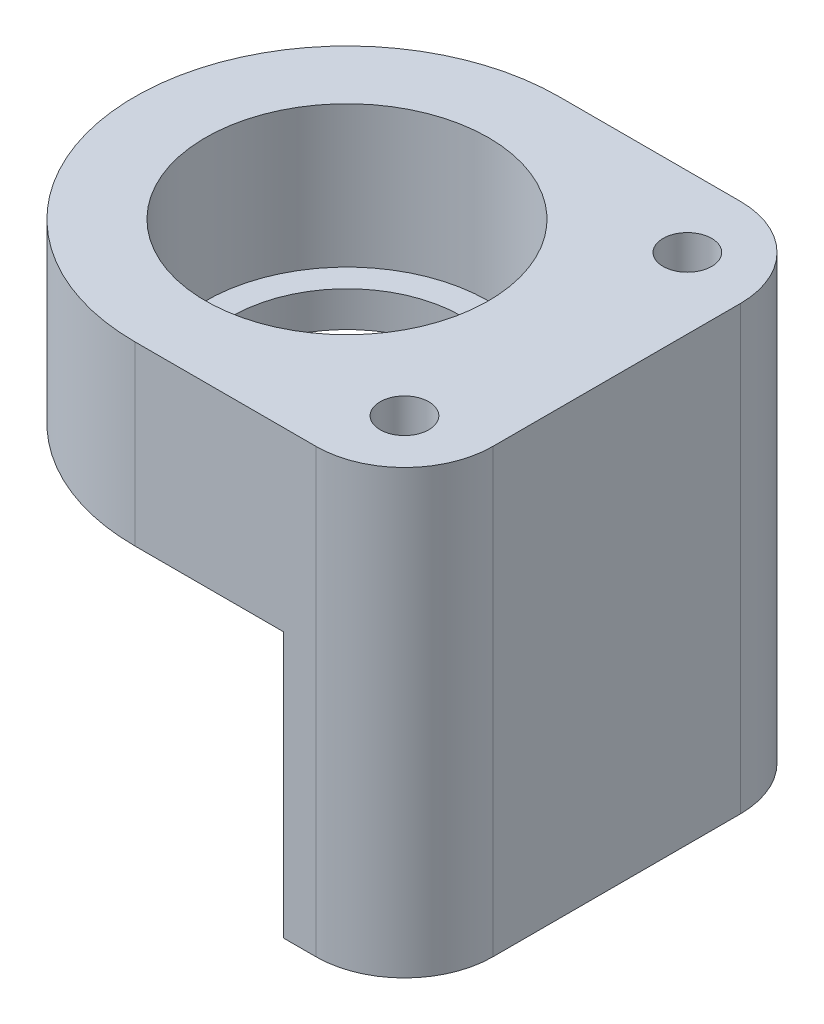
SolidWorks part; units mm, degrees
ref_plane "Front Plane" through (0, 0, 0) normal (0, 0, 1) x (1, 0, 0)
ref_plane "Top Plane" through (0, 0, 0) normal (0, 1, 0) x (1, 0, 0)
ref_plane "Right Plane" through (0, 0, 0) normal (1, 0, 0) x (0, 0, -1)
ref_axis "X" through (88.99, 0, 0) along (-1, 0, 0)
ref_axis "Y" through (0, 55, 0) along (0, -1, 0)
ref_axis "Z" through (0, 0, -88.99) along (0, 0, 1)
sketch "Sketch1" plane through (0, 0, 0) normal (0, 0, 1) x (1, 0, 0)
  line L0 (0, 0) -> (0, 52.8087) construction
  line L4 (-24, 0) -> (-24, 50)
  line L9 (-20, 30) -> (-16, 30)
  line L10 (-16, 34) -> (-16, 50)
  line L13 (-16, 50) -> (-24, 50)
  line L14 (-24, 0) -> (-20, 0)
  line L16 (-20, 0) -> (-20, 30)
  line L17 (-16, 30) -> (-13, 30)
  line L18 (-13, 30) -> (-13, 34)
  line L19 (-13, 34) -> (-16, 34)
  point P3 (0, 0)
  dimension "D2" = 32
  dimension "D3" = 30
  dimension "D4" = 48
  dimension "D5" = 40
  dimension "D6" = 4
  dimension "D7" = 26
  dimension "D10" = 50
revolve "Revolve1" add sketch "Sketch1" angle 360 about L0
sketch "Sketch6" plane through (0, 50, 0) normal (0, 1, 0) x (1, 0, 0)
  line L3 (0, -24) -> (20.5, -24)
  line L4 (30.5, -14) -> (30.5, 14)
  line L5 (20.5, 24) -> (0, 24)
  arc A3 (0, -24) -> (0, 24) centre (0, 0) ccw
  arc A4 (20.5, -24) -> (30.5, -14) centre (20.5, -14) ccw
  arc A5 (30.5, 14) -> (20.5, 24) centre (20.5, 14) ccw
  dimension "D2" = 10
  dimension "D3" = 10
  dimension "D4" = 24
  dimension "D1" = 30.5
extrude "Boss-Extrude1" add sketch "Sketch6" against normal up to surface (50 mm away) up to face at (0, 0, -20)
sketch "Sketch5" plane through (0, 0, 0) normal (0, 1, 0) x (1, 0, 0)
  line L0 (15.0853, -18.6664) -> (20.4834, -35.3012)
  line L5 (-37.3811, 22.9821) -> (-6.9154, 22.9821)
  line L6 (-37.3811, 22.9821) -> (-37.3811, -18.7707)
  line L9 (20.4834, -35.3012) -> (-37.3811, -18.7707)
  line L10 (-6.9154, 22.9821) -> (0, 0)
  line L12 (0, 0) -> (15.0853, -18.6664)
  arc A1 (0, 24) -> (0, -24) centre (0, 0) ccw construction
  circle A3 centre (0, 0) radius 24 construction
  point P4 (0, 24)
  point P7 (-6.9154, 22.9821)
  point P13 (15.0853, -18.7707)
extrude "Cut-Extrude1" cut sketch "Sketch5" along normal blind 30
hole_wizard "Ø3.0mm Dowel Hole1" positions "Sketch7" profile "Sketch8" hole size "Ø3.0" standard "DIN"
sketch "Sketch7" plane through (0, 0, 0) normal (0, -1, 0) x (-1, 0, 0)
  line L0 (-20.5, -24) -> (-16.8161, -24) construction
  line L1 (-30.5, 14) -> (-30.5, -14) construction
  line L2 (0, 24) -> (-20.5, 24) construction
  point P0 (-24.5, -9)
  point P2 (-24.5, 9)
  dimension "D1" = 15
  dimension "D3" = 6
  dimension "D4" = 15
sketch "Sketch8" plane through (24.5, 0, 9) normal (1, 0, 0) x (0, 0, -1)
  line L0 (0, 0) -> (0, 6.9013)
  line L1 (0, 6.9013) -> (1.5, 6)
  line L2 (1.5, 6) -> (1.5, 0)
  line L5 (1.5, 0) -> (0, 0)
  line L10 (0, 6.9013) -> (-1.5, 6) construction
  line L11 (0, -6.35) -> (0, 107.95) construction
  dimension "Hole Dia." = 3
  dimension "Hole Depth" = 6
  dimension "Drill Angle" = 118
hole_wizard "M5 Clearance Hole1" positions "Sketch11" profile "Sketch12" hole size "M5" standard "DIN" end condition up to next
sketch "Sketch11" plane through (0, 0, 0) normal (0, -1, 0) x (-1, 0, 0)
  line L0 (-20.5, -24) -> (-16.8161, -24) construction
  line L1 (-30.5, 14) -> (-30.5, -14) construction
  line L2 (0, 24) -> (-20.5, 24) construction
  point P0 (-22.5, -16)
  point P2 (-22.5, 16)
  dimension "D1" = 8
  dimension "D2" = 8
  dimension "D3" = 8
sketch "Sketch12" plane through (22.5, 0, 16) normal (1, 0, 0) x (0, 0, -1)
  line L0 (0, 0) -> (0, 50)
  line L1 (0, 50) -> (2.75, 50)
  line L2 (2.75, 50) -> (2.75, 0)
  line L5 (2.75, 0) -> (0, 0)
  line L11 (0, -6.35) -> (0, 107.95) construction
  dimension "Thru Hole Dia." = 5.5
  dimension "Thru Hole Depth" = 50
